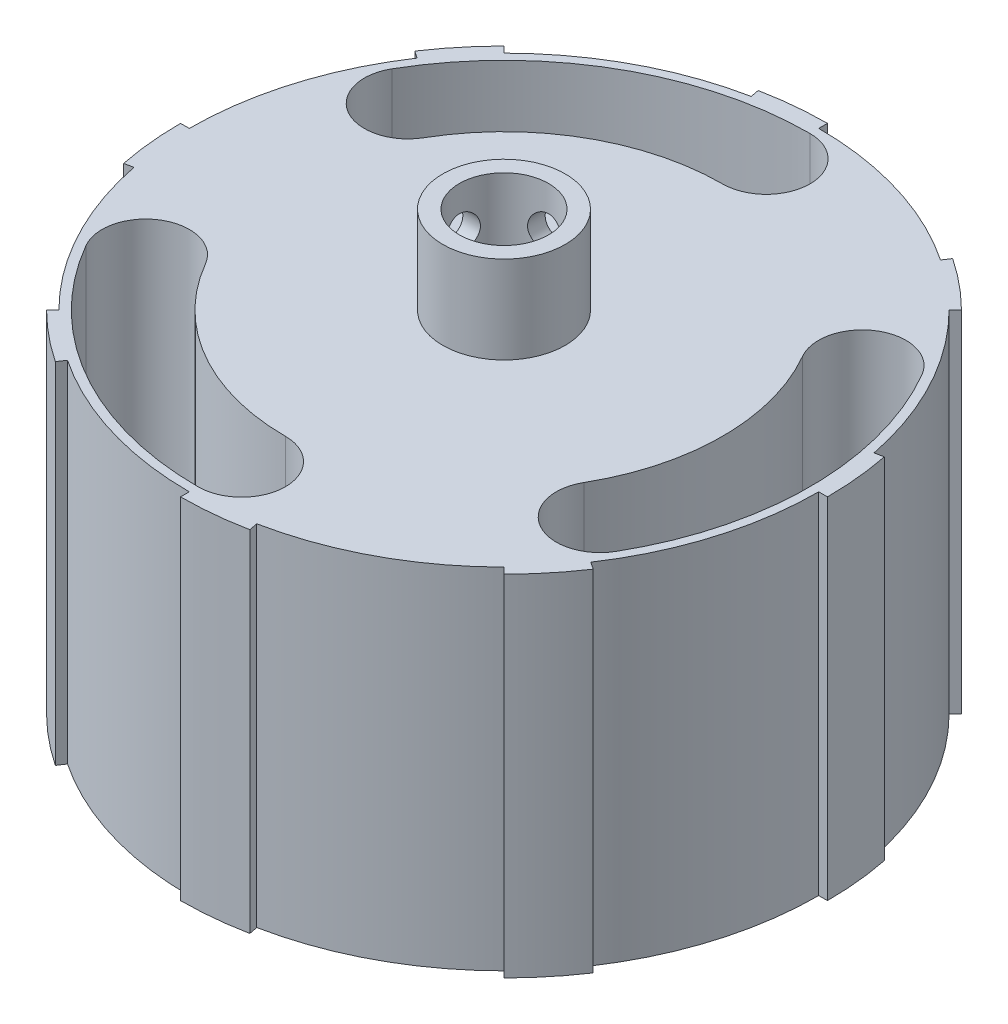
SolidWorks part; units mm, degrees
ref_plane "前视基准面" through (0, 0, 0) normal (0, 0, 1) x (1, 0, 0)
ref_plane "上视基准面" through (0, 0, 0) normal (0, 1, 0) x (1, 0, 0)
ref_plane "右视基准面" through (0, 0, 0) normal (1, 0, 0) x (0, 0, -1)
other "Configuration Table"
sketch "草图1" plane through (0, 0, 0) normal (0, 1, 0) x (1, 0, 0)
  circle A0 centre (0, 0) radius 37
  dimension "D1" = 74
extrude "凸台-拉伸1" add sketch "草图1" along normal blind 40
sketch "草图2" plane through (0, 40, 0) normal (0, 1, 0) x (1, 0, 0)
  circle A0 centre (0, 0) radius 5.1
  dimension "D1" = 10.2
extrude "切除-拉伸1" cut sketch "草图2" against normal blind 40
sketch "草图3" plane through (0, 40, 0) normal (0, 1, 0) x (1, 0, 0)
  line L0 (-1000, 0) -> (49000, 0) construction
  line L1 (0, -1000) -> (0, 49000) construction
  circle A0 centre (0, 0) radius 30
  circle A1 centre (0, 30) radius 5
  circle A3 centre (25.9808, 15) radius 5
  circle A4 centre (30, 0) radius 5
  circle A5 centre (25.9808, -15) radius 5
  circle A7 centre (0, -30) radius 5
  circle A8 centre (-15, -25.9808) radius 5
  circle A9 centre (-25.9808, -15) radius 5
  circle A11 centre (-25.9808, 15) radius 5
  circle A12 centre (-15, 25.9808) radius 5
  circle A13 centre (0, 0) radius 25
  circle A14 centre (0, 0) radius 35
  circle A15 centre (-30, 0) radius 5 [skipped]
  circle A16 centre (15, -25.9808) radius 5 [skipped]
  circle A17 centre (15, 25.9808) radius 5 [skipped]
  point P34 (0, 0)
  dimension "D1" = 60
  dimension "D2" = 10
  dimension "D3" = 12
extrude "切除-拉伸2" cut sketch "草图3" against normal blind 40 contours A0 A11 | A0 A11 | A13 A12 A0 A11 | A12 A14 A11 A0 | A0 A12 | A0 A12 | A1 A14 A12 A0 | A13 A1 A0 A12 | A0 A1 | A0 A1 | A0 A9 | A0 A9 | A9 A14 A8 A0 | A13 A9 A0 A8 | A0 A8 | A0 A8 | A8 A14 A7 A0 | A13 A8 A0 A7 | A0 A7 | A0 A7 | A0 A5 | A0 A5 | A0 A4 | A0 A4 | A0 A3 | A0 A3 | A4 A14 A3 A0 | A13 A4 A0 A3 | A13 A5 A0 A4 | A5 A14 A4 A0 region at (27.8047, 40, 0) region at (32.0453, 40, 0) region at (26.1943, 40, -7.0188) region at (31.6944, 40, -8.4925) region at (31.6944, 40, 8.4925) region at (26.1943, 40, 7.0188) region at (24.0795, 40, -13.9023) region at (27.752, 40, -16.0226) region at (27.752, 40, 16.0226) region at (24.0795, 40, 13.9023) region at (-7.0188, 40, -26.1943) region at (0, 40, -27.8047) region at (0, 40, -32.0453) region at (-8.4925, 40, -31.6944) region at (-8.4925, 40, 31.6944) region at (0, 40, 32.0453) region at (0, 40, 27.8047) region at (-7.0188, 40, 26.1943) region at (-19.1756, 40, -19.1756) region at (-13.9023, 40, -24.0795) region at (-16.0226, 40, -27.752) region at (-23.2019, 40, -23.2019) region at (-23.2019, 40, 23.2019) region at (-16.0226, 40, 27.752) region at (-13.9023, 40, 24.0795) region at (-19.1756, 40, 19.1756) region at (-24.0795, 40, -13.9023) region at (-27.752, 40, -16.0226) region at (-27.752, 40, 16.0226) region at (-24.0795, 40, 13.9023)
sketch "草图4" plane through (0, 40, 0) normal (0, 1, 0) x (1, 0, 0)
  circle A0 centre (0, 0) radius 7
  circle A1 centre (0, 0) radius 5.1
  dimension "D1" = 14
extrude "凸台-拉伸2" add sketch "草图4" along normal mid plane 20
sketch "草图5" plane through (0, 0, 0) normal (0, -1, 0) x (1, 0, 0)
  circle A0 centre (0, 0) radius 5.1
sketch "草图6" plane through (0, 0, 0) normal (0, 0, 1) x (1, 0, 0)
  line L0 (0, 50) -> (0, 45)
  line L1 (5.1, 50) -> (-5.1, 50) construction
  circle A0 centre (0, 45) radius 2
  dimension "D2" = 4
  dimension "D1" = 5
extrude "切除-拉伸3" cut sketch "草图6" against normal up to next contours A0 region at (-1.3742, 43.6258, 0)
sketch "草图7" plane through (0, 0, 0) normal (1, 0, 0) x (0, 0, -1)
  line L0 (0, 50) -> (0, 45)
  line L1 (7, 50) -> (-7, 50) construction
  circle A0 centre (0, 45) radius 2
  dimension "D2" = 4
  dimension "D1" = 5
extrude "切除-拉伸4" cut sketch "草图7" against normal up to next contours A0 region at (0, 43.6258, 1.3742)
sketch "草图10" plane through (0, 0, 0) normal (0, -1, 0) x (1, 0, 0)
  line L0 (0, 0) -> (0, 37)
  line L1 (0, 0) -> (7.2183, 36.2891)
  line L2 (0, 0) -> (14.1593, 34.1835)
  line L3 (0, 0) -> (20.5561, 30.7644)
  line L4 (0, 0) -> (26.163, 26.163)
  line L5 (0, 0) -> (30.7644, 20.5561)
  line L6 (0, 0) -> (34.1835, 14.1593)
  line L7 (0, 0) -> (36.2891, 7.2183)
  line L8 (0, 0) -> (37, 0)
  line L9 (0, 0) -> (36.2891, -7.2183)
  line L10 (0, 0) -> (34.1835, -14.1593)
  line L11 (0, 0) -> (30.7644, -20.5561)
  line L12 (0, 0) -> (26.163, -26.163)
  line L13 (0, 0) -> (20.5561, -30.7644)
  line L14 (0, 0) -> (14.1593, -34.1835)
  line L15 (0, 0) -> (7.2183, -36.2891)
  line L16 (0, 0) -> (0, -37)
  line L17 (0, 0) -> (-7.2183, -36.2891)
  line L18 (0, 0) -> (-14.1593, -34.1835)
  line L19 (0, 0) -> (-20.5561, -30.7644)
  line L20 (0, 0) -> (-26.163, -26.163)
  line L21 (0, 0) -> (-30.7644, -20.5561)
  line L22 (0, 0) -> (-34.1835, -14.1593)
  line L23 (0, 0) -> (-36.2891, -7.2183)
  line L24 (0, 0) -> (-37, 0)
  line L25 (0, 0) -> (-36.2891, 7.2183)
  line L26 (0, 0) -> (-34.1835, 14.1593)
  line L27 (0, 0) -> (-30.7644, 20.5561)
  line L28 (0, 0) -> (-26.163, 26.163)
  line L29 (0, 0) -> (-20.5561, 30.7644)
  line L30 (0, 0) -> (-14.1593, 34.1835)
  line L31 (0, 0) -> (-7.2183, 36.2891)
  circle A0 centre (0, 0) radius 37
  circle A1 centre (0, 0) radius 36
  point P38 (0, 0)
  circle M14 centre (0, 0) radius 37
  dimension "D1" = 72
  dimension "D2" = 37
  dimension "D3" = 32
extrude "切除-拉伸7" cut sketch "草图10" against normal up to next contours A1 L26 L25 M14 | A1 L27 L26 M14 | A1 L28 L27 M14 | A1 L30 L29 M14 | A1 L31 L30 M14 | A1 L0 L31 M14 | A1 L2 L1 M14 | A1 L3 L2 M14 | A1 L4 L3 M14 | A1 L6 L5 M14 | A1 L7 L6 M14 | A1 L8 L7 M14 | A1 L10 L9 M14 | A1 L11 L10 M14 | A1 L12 L11 M14 | A1 L14 L13 M14 | A1 L15 L14 M14 | A1 L16 L15 M14 | A1 L18 L17 M14 | A1 L19 L18 M14 | A1 L20 L19 M14 | A1 L22 L21 M14 | A1 L23 L22 M14 | A1 L24 L23 M14 region at (-3.5721, 0, 36.2682) region at (10.579, 0, 34.8744) region at (17.1794, 0, 32.1405) region at (23.1196, 0, 28.1713) region at (32.1405, 0, 17.1794) region at (34.8744, 0, 10.579) region at (36.2682, 0, 3.5721) region at (34.8744, 0, -10.579) region at (32.1405, 0, -17.1794) region at (28.1713, 0, -23.1196) region at (17.1794, 0, -32.1405) region at (10.579, 0, -34.8744) region at (3.5721, 0, -36.2682) region at (-10.579, 0, -34.8744) region at (-17.1794, 0, -32.1405) region at (-23.1196, 0, -28.1713) region at (-32.1405, 0, -17.1794) region at (-34.8744, 0, -10.579) region at (-36.2682, 0, -3.5721) region at (-34.8744, 0, 10.579) region at (-32.1405, 0, 17.1794) region at (-28.1713, 0, 23.1196) region at (-17.1794, 0, 32.1405) region at (-10.579, 0, 34.8744)
